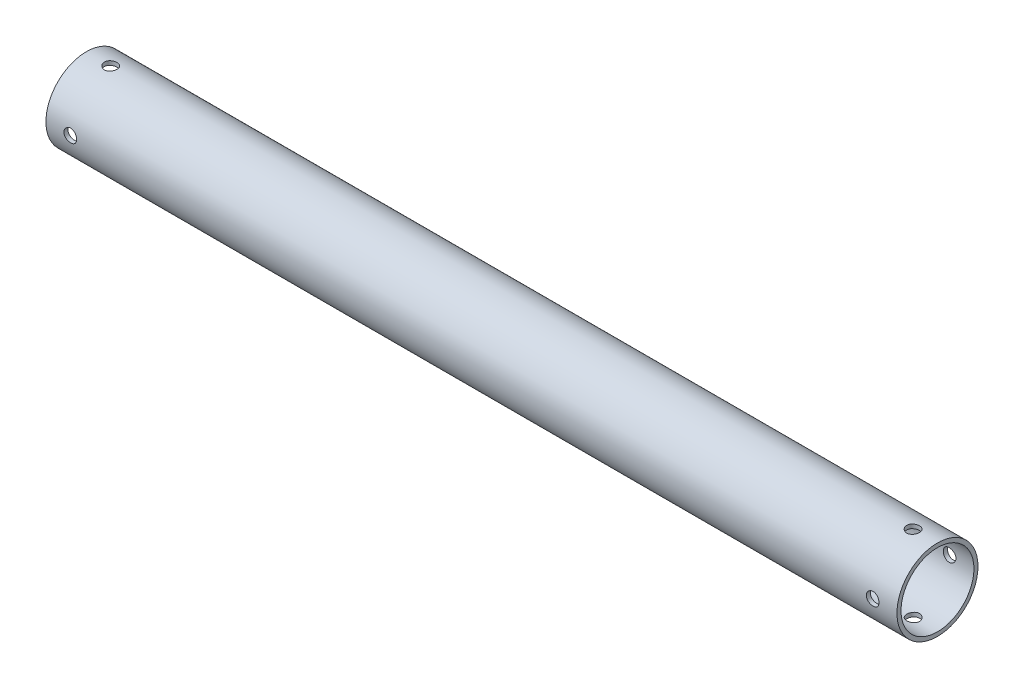
SolidWorks part; units mm, degrees
material "PC High Viscosity"
ref_plane "Front Plane" through (0, 0, 0) normal (0, 0, 1) x (1, 0, 0)
ref_plane "Top Plane" through (0, 0, 0) normal (0, 1, 0) x (1, 0, 0)
ref_plane "Right Plane" through (0, 0, 0) normal (1, 0, 0) x (0, 0, -1)
sketch "Sketch1" plane through (0, 0, 0) normal (1, 0, 0) x (0, 0, -1)
  circle A0 centre (0, 0) radius 15.875
  dimension "D1" = 31.75
extrude "Extrude-Thin1" add sketch "Sketch1" along normal mid plane 333.375 thin thin type one direction reverse wall 1.5875
sketch "Sketch2" plane through (0, 0, 0) normal (0, 0, 1) x (1, 0, 0)
  line L0 (-166.6875, -15.875) -> (166.6875, -15.875) construction
  line L1 (104.4125, -15.875) -> (125.4125, -15.875)
  line L2 (104.4125, -15.875) -> (104.4125, 15.875)
  line L3 (104.4125, 15.875) -> (125.4125, 15.875)
  line L4 (125.4125, -15.875) -> (125.4125, 15.875)
  line L5 (166.6875, 15.875) -> (-166.6875, 15.875) construction
  line L6 (166.6875, -15.875) -> (166.6875, 15.875) construction
  line L7 (0, 0) -> (0, 11.1276) construction
  line L8 (-125.4125, -15.875) -> (-125.4125, 15.875)
  line L9 (-104.4125, 15.875) -> (-125.4125, 15.875)
  line L10 (-104.4125, -15.875) -> (-104.4125, 15.875)
  line L11 (-104.4125, -15.875) -> (-125.4125, -15.875)
  line L13 (166.6875, -15.875) -> (164.3634, -15.875)
  line L14 (166.6875, -15.875) -> (166.6875, 15.875)
  line L15 (166.6875, 15.875) -> (164.3634, 15.875)
  line L16 (164.3634, -15.875) -> (164.3634, 15.875)
  dimension "D1" = 41.275
  dimension "D2" = 21
  dimension "D3" = 2.3241
sketch "Sketch3" plane through (0, 0, 0) normal (0, 0, 1) x (1, 0, 0)
  line L0 (166.6875, -14.2875) -> (166.6875, 14.2875) construction
  line L1 (-166.6875, 15.875) -> (-166.6875, -15.875) construction
  circle A0 centre (157.1625, 0) radius 2.4892
  circle A1 centre (-157.1625, 0) radius 2.4892
  dimension "D1" = 4.9784
  dimension "D2" = 9.525
  dimension "D3" = 9.525
extrude "Cut-Extrude1" cut sketch "Sketch3" against normal through all both and the other way through all
sketch "Sketch4" plane through (0, 0, 0) normal (0, 1, 0) x (1, 0, 0)
  line L0 (166.6875, -14.2875) -> (166.6875, 14.2875) construction
  line L1 (0, 15.875) -> (0, -15.875) construction
  line L2 (-154.6733, -15.875) -> (154.6733, -15.875) construction
  line L3 (154.6733, 15.875) -> (-154.6733, 15.875) construction
  circle A0 centre (157.1625, 0) radius 2.4892
  circle A1 centre (-157.1625, 0) radius 2.4892
  dimension "D1" = 4.9784
  dimension "D2" = 9.525
extrude "Cut-Extrude2" cut sketch "Sketch4" against normal through all both and the other way through all
equation "\"D2@Sketch2\"=21mm"
